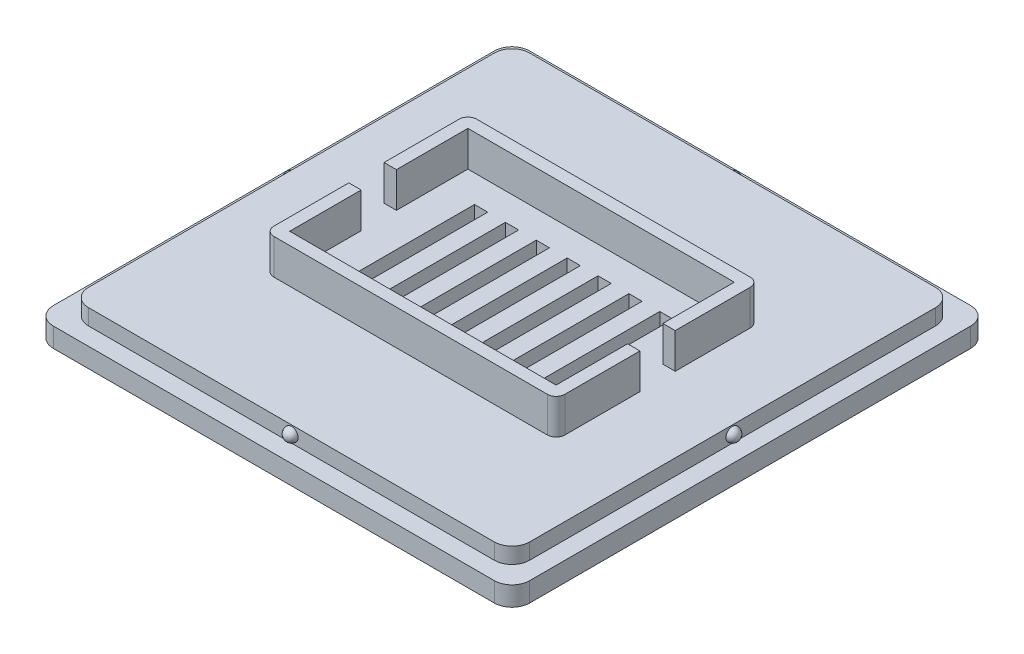
SolidWorks part; units mm, degrees
note: The reader was unsure of these and kept them because the rebuilt part matched: shared geometry of "草图9<8>".
ref_plane "前视基准面" through (0, 0, 0) normal (0, 0, 1) x (1, 0, 0)
ref_plane "上视基准面" through (0, 0, 0) normal (0, 1, 0) x (1, 0, 0)
ref_plane "右视基准面" through (0, 0, 0) normal (1, 0, 0) x (0, 0, -1)
sketch "草图1" plane through (0, 0, 0) normal (0, 1, 0) x (1, 0, 0)
  line L1 (-34.2682, 36.789) -> (19.7318, 36.789)
  line L2 (-34.2682, 36.789) -> (-34.2682, -17.211)
  line L3 (-34.2682, -17.211) -> (19.7318, -17.211)
  line L4 (19.7318, 36.789) -> (19.7318, -17.211)
  line L5 (-7.2682, -17.211) -> (-7.2682, 36.789) construction
  line L6 (-34.2682, 9.789) -> (19.7318, 9.789) construction
  line L7 (-32.2682, 34.789) -> (17.7318, 34.789)
  line L8 (-32.2682, 34.789) -> (-32.2682, -15.211)
  line L9 (-32.2682, -15.211) -> (17.7318, -15.211)
  line L10 (17.7318, 34.789) -> (17.7318, -15.211)
  line L11 (-7.2682, -15.211) -> (-7.2682, 34.789) construction
  line L12 (-32.2682, 9.789) -> (17.7318, 9.789) construction
  point P0 (-7.2682, 9.789)
  point P4 (-7.2682, 9.789)
  dimension "D1" = 54
  dimension "D2" = 54
  dimension "D3" = 50
  dimension "D4" = 50
extrude "凸台-拉伸2" add sketch "草图1" along normal blind 2.2 contours L1 L4 L3 L2
sketch "草图7" plane through (0, 2.2, 0) normal (0, 1, 0) x (1, 0, 0)
  line L0 (-34.2682, 36.789) -> (-34.2682, -17.211) construction
  line L1 (-32.2682, -15.211) -> (17.7318, -15.211)
  line L2 (-32.2682, -15.211) -> (-32.2682, 34.789)
  line L3 (-32.2682, 34.789) -> (17.7318, 34.789)
  line L4 (17.7318, -15.211) -> (17.7318, 34.789)
  line L5 (-7.2682, 34.789) -> (-7.2682, -15.211) construction
  line L6 (-32.2682, 9.789) -> (17.7318, 9.789) construction
  line L7 (-34.2682, -17.211) -> (19.7318, -17.211) construction
  line L8 (-34.2682, 36.789) -> (19.7318, 36.789) construction
  line L9 (19.7318, 36.789) -> (19.7318, -17.211) construction
  point P0 (-7.2682, 9.789)
  dimension "D1" = 2
  dimension "D2" = 2
  dimension "D3" = 2
  dimension "D4" = 2
extrude "凸台-拉伸3" add sketch "草图7" along normal blind 1.8
ref_plane "基准面3" through (-32.2682, 4, 15.211) normal (0, 0, 1) x (1, 0, 0)
sketch "草图9" plane through (0, 4, 0) normal (0, 1, 0) x (1, 0, 0)
  line L0 (-82.2682, 9.789) -> (17.7318, 9.789)
  line L1 (17.7318, 9.789) -> (-7.2682, -15.211)
  line L2 (-7.2682, -15.211) -> (-7.2682, 34.789)
  line L3 (-4.5182, 2.789) -> (-4.5182, 16.789)
  line L4 (17.7318, -15.211) -> (17.7318, 34.789)
  line L5 (17.7318, 34.789) -> (-32.2682, 34.789)
  line L6 (-32.2682, 34.789) -> (-32.2682, -15.211)
  line L7 (-32.2682, -15.211) -> (17.7318, -15.211)
  line L8 (17.7318, -15.211) -> (17.7318, 34.789)
  line L9 (17.7318, 34.789) -> (-32.2682, 34.789)
  line L10 (-32.2682, 34.789) -> (-32.2682, -15.211)
  line L11 (-32.2682, -15.211) -> (17.7318, -15.211)
  line L12 (-22.7682, -1.711) -> (8.2318, -1.711)
  line L13 (-23.7682, -0.711) -> (-23.7682, 7.789)
  line L14 (-22.7682, 21.289) -> (8.2318, 21.289)
  line L15 (9.2318, -0.711) -> (9.2318, 7.789)
  line L16 (-7.2682, 21.289) -> (-7.2682, -1.711) construction
  line L17 (-23.7682, 9.789) -> (9.2318, 9.789) construction
  line L18 (-22.3682, -0.311) -> (7.8318, -0.311)
  line L19 (-22.3682, -0.311) -> (-22.3682, 7.789)
  line L20 (-22.3682, 19.889) -> (7.8318, 19.889)
  line L21 (7.8318, -0.311) -> (7.8318, 7.789)
  line L22 (-7.2682, 19.889) -> (-7.2682, -0.311) construction
  line L23 (-22.3682, 9.789) -> (7.8318, 9.789) construction
  line L24 (-8.0182, 2.789) -> (-6.5182, 2.789)
  line L25 (-8.0182, 2.789) -> (-8.0182, 16.789)
  line L26 (-8.0182, 16.789) -> (-6.5182, 16.789)
  line L27 (-6.5182, 2.789) -> (-6.5182, 16.789)
  line L28 (-7.2682, 16.789) -> (-7.2682, 2.789) construction
  line L29 (-8.0182, 9.789) -> (-6.5182, 9.789) construction
  line L30 (-3.0182, 2.789) -> (-3.0182, 16.789)
  line L31 (-4.5182, 2.789) -> (-3.0182, 2.789)
  line L32 (-4.5182, 16.789) -> (-3.0182, 16.789)
  line L33 (-1.0182, 2.789) -> (-1.0182, 16.789)
  line L34 (0.4818, 2.789) -> (0.4818, 16.789)
  line L35 (-1.0182, 2.789) -> (0.4818, 2.789)
  line L36 (-1.0182, 16.789) -> (0.4818, 16.789)
  line L37 (2.4818, 2.789) -> (2.4818, 16.789)
  line L38 (3.9818, 2.789) -> (3.9818, 16.789)
  line L39 (2.4818, 2.789) -> (3.9818, 2.789)
  line L40 (2.4818, 16.789) -> (3.9818, 16.789)
  line L41 (-11.5182, 2.789) -> (-11.5182, 16.789)
  line L42 (-10.0182, 2.789) -> (-10.0182, 16.789)
  line L43 (-11.5182, 2.789) -> (-10.0182, 2.789)
  line L44 (-11.5182, 16.789) -> (-10.0182, 16.789)
  line L45 (-15.0182, 2.789) -> (-15.0182, 16.789)
  line L46 (-13.5182, 2.789) -> (-13.5182, 16.789)
  line L47 (-15.0182, 2.789) -> (-13.5182, 2.789)
  line L48 (-15.0182, 16.789) -> (-13.5182, 16.789)
  line L49 (-18.5182, 2.789) -> (-18.5182, 16.789)
  line L50 (-17.0182, 2.789) -> (-17.0182, 16.789)
  line L51 (-18.5182, 2.789) -> (-17.0182, 2.789)
  line L52 (-18.5182, 16.789) -> (-17.0182, 16.789)
  line L53 (-23.7682, 7.789) -> (-22.3682, 7.789)
  line L54 (-23.7682, 9.789) -> (-22.3682, 9.789)
  line L55 (7.8318, 11.789) -> (9.2318, 11.789)
  line L56 (-23.7682, 11.789) -> (-22.3682, 11.789)
  line L58 (-23.7682, 11.789) -> (-23.7682, 20.289)
  line L59 (-22.3682, 11.789) -> (-22.3682, 19.889)
  line L60 (7.8318, 7.789) -> (9.2318, 7.789)
  line L61 (7.8318, 11.789) -> (7.8318, 19.889)
  line L62 (9.2318, 11.789) -> (9.2318, 20.289)
  arc A0 (8.2318, -1.711) -> (9.2318, -0.711) centre (8.2318, -0.711) ccw
  arc A1 (8.2318, 21.289) -> (9.2318, 20.289) centre (8.2318, 20.289) cw
  arc A2 (-22.7682, -1.711) -> (-23.7682, -0.711) centre (-22.7682, -0.711) cw
  arc A3 (-23.7682, 20.289) -> (-22.7682, 21.289) centre (-22.7682, 20.289) cw
  point P2 (-7.2682, 9.789)
  point P7 (-32.2682, 9.789)
  point P18 (9.2318, 21.289)
  point P21 (-23.7682, -1.711)
  point P24 (-23.7682, 21.289)
  point P25 (-7.2682, 9.789)
  point P29 (-7.2682, 9.789)
  dimension "D4" = 1
  dimension "D2" = 23
  dimension "D3" = 33
  dimension "D5" = 20.2
  dimension "D6" = 30.2
  dimension "D7" = 14
  dimension "D8" = 1.5
  dimension "D11" = 2
  dimension "D12" = 2
  dimension "D13" = 2
  dimension "D14" = 2
  dimension "D1" = 0
  dimension "D9" = 4
  dimension "D10" = 4
extrude "凸台-拉伸5" add sketch "草图9" along normal blind 4 contours L18 L2 L12 L1 | L62 A1 L14 A3 L58 L56 L59 L20 L61 L55
extrude "切除-拉伸2" cut sketch "草图9<8>" against normal blind 10 contours L44 L41 L0 L42 | L41 L43 L42 L0 | L25 L26 L27 L24 | L46 L48 L45 L47 | L50 L52 L49 L51 | L30 L32 L3 L31 | L34 L36 L33 L35 | L38 L40 L37 L39
sketch "草图9<8>" plane through (0, 4, 0) normal (0, 1, 0) x (1, 0, 0) same geometry as "草图9"
fillet "圆角1" radius 2 8 edges at (19.7318, 1.1, -36.789) (17.7318, 3.1, -34.789) (17.7318, 3.1, 15.211) (19.7318, 1.1, 17.211) (-32.2682, 3.1, 15.211) (-34.2682, 1.1, 17.211) (-32.2682, 3.1, -34.789) (-34.2682, 1.1, -36.789)
sketch "草图12" plane through (0, 0, 15.211) normal (0, 0, 1) x (1, 0, 0)
  line L0 (-7.2682, 4) -> (-7.2682, 2.2)
  line L1 (-32.2682, 4) -> (17.7318, 4) construction
  line L2 (-30.2682, 2.2) -> (15.7318, 2.2) construction
  arc A0 (-7.2682, 2.35) -> (-7.2682, 3.85) centre (-7.2682, 3.1) ccw
  dimension "D1" = 1.5
revolve "旋转-薄壁5" add sketch "草图12" angle 360 about L0
sketch "草图13" plane through (-32.2682, 0, 0) normal (-1, 0, 0) x (0, 0, 1)
  line L0 (-9.789, 4) -> (-9.789, 2.2)
  line L1 (-34.789, 2.2) -> (15.211, 2.2) construction
  arc A0 (-9.789, 2.35) -> (-9.789, 3.85) centre (-9.789, 3.1) ccw
  dimension "D1" = 1.5
revolve "旋转-薄壁6" add sketch "草图13" angle 360 about L0
sketch "草图14" plane through (0, 0, -36.789) normal (0, 0, -1) x (-1, 0, 0)
  line L0 (7.2682, 4) -> (7.2682, 2.2)
  line L1 (-15.7318, 2.2) -> (30.2682, 2.2) construction
  arc A0 (7.2682, 3.85) -> (7.2682, 2.35) centre (7.2682, 3.1) ccw
  dimension "D1" = 1.5
sketch "草图15" plane through (17.7318, 0, 0) normal (1, 0, 0) x (0, 0, -1)
  line L0 (9.789, 4) -> (9.789, 2.2)
  line L1 (-15.211, 4) -> (34.789, 4) construction
  line L2 (-13.211, 2.2) -> (32.789, 2.2) construction
  arc A0 (9.789, 2.35) -> (9.789, 3.85) centre (9.789, 3.1) ccw
  dimension "D1" = 1.5
revolve "旋转-薄壁8" add sketch "草图15" angle 332 about L0
sketch "草图16" plane through (0, 0, -34.789) normal (0, 0, -1) x (-1, 0, 0)
  line L0 (7.2682, 4) -> (7.2682, 2.2) construction
  line L1 (7.2682, 4) -> (7.2682, 2.2)
  arc A0 (7.2682, 3.85) -> (7.2682, 2.35) centre (7.2682, 3.1) ccw construction
  arc A1 (7.2682, 3.85) -> (7.2682, 2.35) centre (7.2682, 3.1) ccw
revolve "旋转-薄壁9" add sketch "草图16" angle 360 about L1
